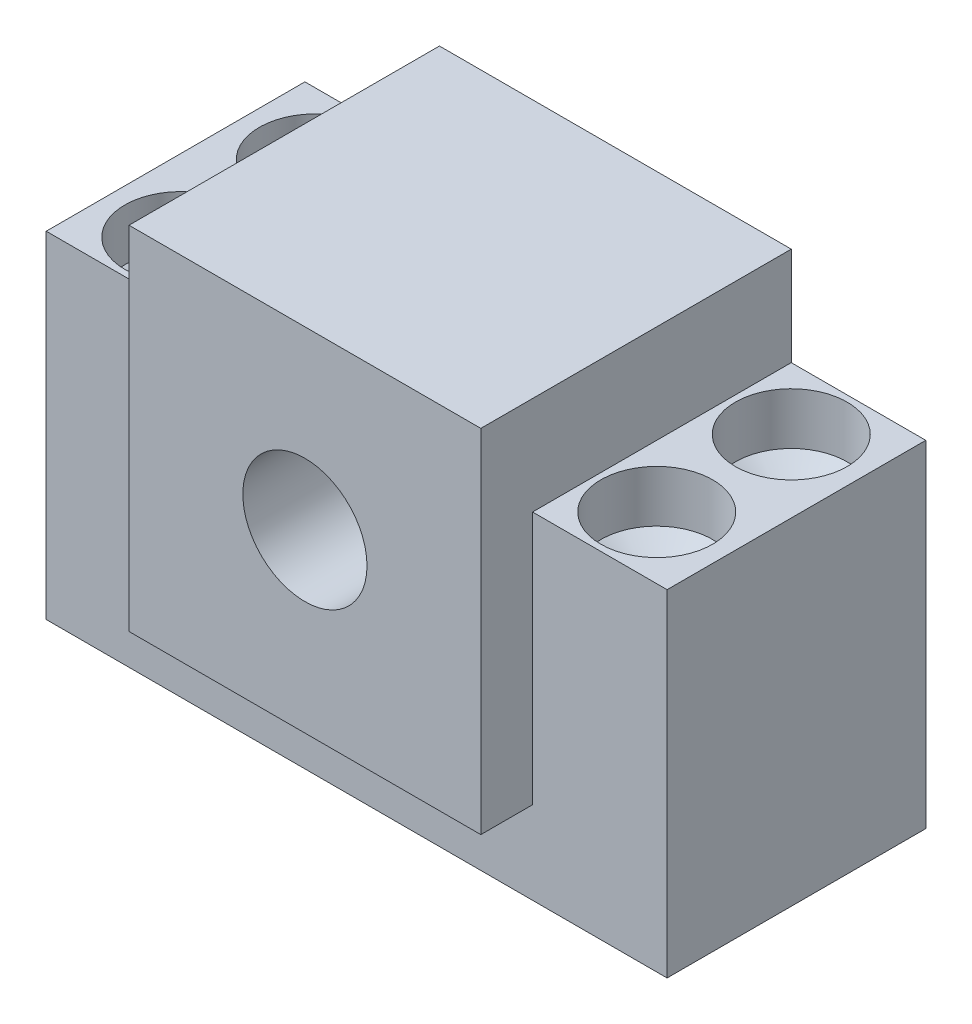
SolidWorks part; units mm, degrees
ref_plane "Front Plane" through (0, 0, 0) normal (0, 0, 1) x (1, 0, 0)
ref_plane "Top Plane" through (0, 0, 0) normal (0, 1, 0) x (1, 0, 0)
ref_plane "Right Plane" through (0, 0, 0) normal (1, 0, 0) x (0, 0, -1)
sketch "Sketch1" plane through (0, 0, 0) normal (0, 0, 1) x (1, 0, 0)
  line L1 (-30, 16.25) -> (17, 16.25)
  line L2 (-30, 16.25) -> (-30, -16.25)
  line L3 (-30, -16.25) -> (30, -16.25)
  line L4 (30, 16.25) -> (30, -16.25)
  line L5 (-30, 16.25) -> (30, -16.25) construction
  line L6 (-30, -16.25) -> (30, 16.25) construction
  line L7 (-17, 25.75) -> (17, 25.75)
  line L8 (-17, 25.75) -> (-17, -8.25)
  line L9 (17, 16.25) -> (30, 16.25)
  line L10 (-17, -8.25) -> (17, -8.25)
  line L11 (17, 25.75) -> (17, -8.25)
  line L12 (-17, 25.75) -> (17, -8.25) construction
  line L13 (-17, -8.25) -> (17, 25.75) construction
  point P0 (0, 0)
  point P6 (0, 8.75)
  dimension "D1" = 60
  dimension "D2" = 32.5
  dimension "D3" = 34
  dimension "D4" = 34
  dimension "D5" = 30
  dimension "D6" = 25
extrude "Boss-Extrude1" add sketch "Sketch1" along normal blind 25 contours L9 L11 L10 L8 L1 L2 L3 L4 region at (-23.5, 15.5676, 0)
extrude "Boss-Extrude2" add sketch "Sketch1<3>" along normal blind 30 contours L11 L7 L8 L1 | L11 L1 L8 L10 region at (0, 21, 0) region at (0, 4, 0)
sketch "Sketch1<3>" plane through (0, 0, 0) normal (0, 0, 1) x (1, 0, 0) same geometry as "Sketch1"
hole_wizard "Ø6.6 (6.6) Diameter Hole1" positions "Sketch3" profile "Sketch2" hole size "Ø6.6" standard "ISO" end condition through all
sketch "Sketch3" plane through (0, 16.25, 0) normal (0, 1, 0) x (1, 0, 0)
  line L0 (17, 0) -> (30, 0) construction
  line L1 (-30, 0) -> (-17, 0) construction
  line L2 (-30, -25) -> (-30, 0) construction
  line L3 (30, -25) -> (30, 0) construction
  point P0 (-23, -19)
  point P2 (-23, -6)
  point P4 (23, -6)
  point P6 (23, -19)
  dimension "D1" = 46
  dimension "D2" = 46
  dimension "D3" = 6
  dimension "D4" = 6
  dimension "D5" = 13
  dimension "D6" = 13
  dimension "D7" = 7
  dimension "D8" = 7
  dimension "D9" = 7
sketch "Sketch2" plane through (-23, 16.25, 19) normal (1, 0, 0) x (0, 0, 1)
  line L0 (0, 0) -> (0, 32.5)
  line L1 (0, 32.5) -> (3.3, 32.5)
  line L2 (3.3, 32.5) -> (3.3, 0)
  line L5 (3.3, 0) -> (0, 0)
  line L11 (0, -6.35) -> (0, 107.95) construction
  dimension "Thru Hole Dia." = 6.6
  dimension "Thru Hole Depth" = 32.5
sketch "Sketch4" plane through (0, 0, 30) normal (0, 0, 1) x (1, 0, 0)
  line L0 (-17, 25.75) -> (17, 25.75) construction
  line L1 (-17, 25.75) -> (-17, -8.25) construction
  circle A0 centre (0, 8.75) radius 6
  dimension "D3" = 12
  dimension "D1" = 17
  dimension "D2" = 17
extrude "Cut-Extrude1" cut sketch "Sketch4" against normal blind 30
hole_wizard "Ø10.8 (10.8) Diameter Hole1" positions "Sketch6" profile "Sketch5" hole size "Ø10.8" standard "ISO"
sketch "Sketch6" plane through (0, 16.25, 0) normal (0, 1, 0) x (1, 0, 0)
  line L0 (30, -25) -> (30, 0) construction
  point P0 (-23, -19)
  point P3 (-23, -6)
  point P6 (23, -6)
  point P9 (23, -19)
  dimension "D1" = 7
sketch "Sketch5" plane through (-23, 16.25, 19) normal (1, 0, 0) x (0, 0, 1)
  line L0 (0, 0) -> (0, 8.2446)
  line L1 (0, 8.2446) -> (5.4, 5)
  line L2 (5.4, 5) -> (5.4, 0)
  line L5 (5.4, 0) -> (0, 0)
  line L10 (0, 8.2446) -> (-5.4, 5) construction
  line L11 (0, -6.35) -> (0, 107.95) construction
  dimension "Hole Dia." = 10.8
  dimension "Hole Depth" = 5
  dimension "Drill Angle" = 118
